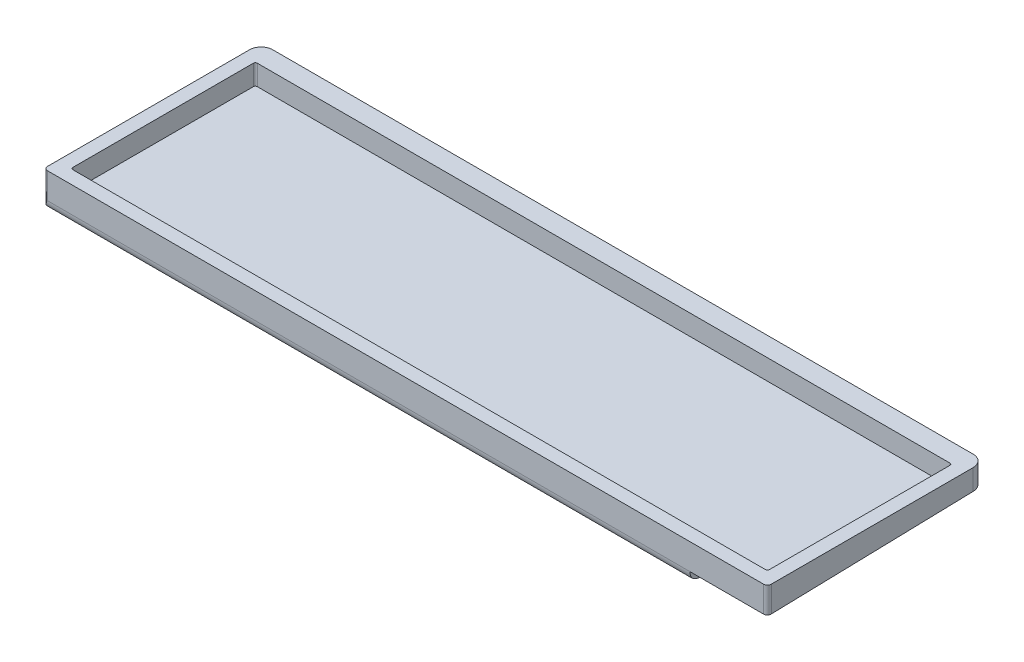
SolidWorks part; units mm, degrees
ref_plane "Front Plane" through (0, 0, 0) normal (0, 0, 1) x (1, 0, 0)
ref_plane "Top Plane" through (0, 0, 0) normal (0, 1, 0) x (1, 0, 0)
ref_plane "Right Plane" through (0, 0, 0) normal (1, 0, 0) x (0, 0, -1)
sketch "Sketch1" plane through (0, 0, 0) normal (0, 1, 0) x (1, 0, 0)
  line L1 (-178.825, 47.625) -> (178.825, 47.625)
  line L2 (-179.825, 46.625) -> (-179.825, -46.625)
  line L3 (-178.825, -47.625) -> (178.825, -47.625)
  line L4 (179.825, 46.625) -> (179.825, -46.625)
  line L5 (-179.825, 47.625) -> (179.825, -47.625) construction
  line L6 (-179.825, -47.625) -> (179.825, 47.625) construction
  arc A0 (178.825, -47.625) -> (179.825, -46.625) centre (178.825, -46.625) ccw
  arc A1 (178.825, 47.625) -> (179.825, 46.625) centre (178.825, 46.625) cw
  arc A2 (-179.825, -46.625) -> (-178.825, -47.625) centre (-178.825, -46.625) ccw
  arc A3 (-178.825, 47.625) -> (-179.825, 46.625) centre (-178.825, 46.625) ccw
  circle A4 centre (157.075, 19.175) radius 1.1
  circle A5 centre (136.925, -16.775) radius 1.1
  circle A6 centre (-153.475, 33.725) radius 1.1
  circle A7 centre (17.925, 22.275) radius 1.1
  circle A8 centre (17.875, -35.075) radius 1.1
  circle A9 centre (-130.375, -35.725) radius 1.1
  point P0 (0, 0)
  dimension "D3" = 1
  dimension "D4" = 2.2
  dimension "D7" = 2.2
  dimension "D8" = 2.2
  dimension "D9" = 2.2
  dimension "D10" = 2.2
  dimension "D11" = 2.2
  dimension "D1" = 359.65
  dimension "D2" = 95.25
  dimension "D5" = 22.75
  dimension "D6" = 28.45
  dimension "D12" = 42.9
  dimension "D13" = 30.85
  dimension "D14" = 25.35
  dimension "D15" = 161.9
  dimension "D16" = 12.55
  dimension "D17" = 161.95
  dimension "D18" = 11.9
  dimension "D19" = 49.45
  dimension "D20" = 13.9
  dimension "D21" = 26.35
sketch "Sketch2" plane through (0, 0, 0) normal (0, 1, 0) x (1, 0, 0)
  line L0 (-179.825, 46.625) -> (-179.825, -46.625) construction
  line L1 (-178.825, -47.625) -> (178.825, -47.625) construction
  line L2 (179.825, 46.625) -> (179.825, -46.625) construction
  line L3 (-178.825, 47.625) -> (178.825, 47.625) construction
  line L4 (-179.825, 46.625) -> (-179.825, -46.625)
  line L5 (-178.825, -47.625) -> (178.825, -47.625)
  line L6 (179.825, 46.625) -> (179.825, -46.625)
  line L7 (-178.825, 47.625) -> (178.825, 47.625)
  line L9 (-180.825, 57.625) -> (180.825, 57.625)
  line L10 (-186.825, 51.625) -> (-186.825, -52.625)
  line L11 (-184.825, -54.625) -> (184.825, -54.625)
  line L12 (186.825, 51.625) -> (186.825, -52.625)
  circle A0 centre (157.075, 19.175) radius 1.1 construction
  circle A1 centre (136.925, -16.775) radius 1.1 construction
  circle A2 centre (17.875, -35.075) radius 1.1 construction
  circle A3 centre (17.925, 22.275) radius 1.1 construction
  circle A4 centre (-153.475, 33.725) radius 1.1 construction
  circle A5 centre (-130.375, -35.725) radius 1.1 construction
  arc A6 (-179.825, -46.625) -> (-178.825, -47.625) centre (-178.825, -46.625) ccw construction
  arc A7 (178.825, -47.625) -> (179.825, -46.625) centre (178.825, -46.625) ccw construction
  arc A8 (179.825, 46.625) -> (178.825, 47.625) centre (178.825, 46.625) ccw construction
  arc A9 (-178.825, 47.625) -> (-179.825, 46.625) centre (-178.825, 46.625) ccw construction
  circle A10 centre (157.075, 19.175) radius 1.1
  circle A11 centre (136.925, -16.775) radius 1.1
  circle A12 centre (17.875, -35.075) radius 1.1
  circle A13 centre (17.925, 22.275) radius 1.1
  circle A14 centre (-153.475, 33.725) radius 1.1
  circle A15 centre (-130.375, -35.725) radius 1.1
  arc A16 (-179.825, -46.625) -> (-178.825, -47.625) centre (-178.825, -46.625) ccw
  arc A17 (178.825, -47.625) -> (179.825, -46.625) centre (178.825, -46.625) ccw
  arc A18 (179.825, 46.625) -> (178.825, 47.625) centre (178.825, 46.625) ccw
  arc A19 (-178.825, 47.625) -> (-179.825, 46.625) centre (-178.825, 46.625) ccw
  arc A20 (180.825, 57.625) -> (186.825, 51.625) centre (180.825, 51.625) cw
  arc A21 (-180.825, 57.625) -> (-186.825, 51.625) centre (-180.825, 51.625) ccw
  arc A22 (184.825, -54.625) -> (186.825, -52.625) centre (184.825, -52.625) ccw
  arc A23 (-186.825, -52.625) -> (-184.825, -54.625) centre (-184.825, -52.625) ccw
  point P30 (0, 0)
  dimension "D5" = 6
  dimension "D6" = 2
  dimension "D1" = 10
  dimension "D2" = 7
  dimension "D3" = 7
  dimension "D4" = 7
extrude "Boss-Extrude1" add sketch "Sketch2" along normal blind 10.5 contours L10 A23 L11 A22 L12 A20 L9 A21 A19 L7 A18 L6 A17 L5 A16 L4 region at (0, 0, -53.7235)
sketch "Sketch4" plane through (0, 0, 0) normal (0, -1, 0) x (1, 0, 0)
  line L0 (186.825, -51.625) -> (186.825, 52.625) construction
  line L1 (-180.825, -57.625) -> (180.825, -57.625) construction
  line L2 (-186.825, -51.625) -> (-186.825, 52.625) construction
  line L3 (-184.825, 54.625) -> (184.825, 54.625) construction
  line L4 (-179.825, 46.625) -> (-179.825, -46.625)
  line L5 (178.825, 47.625) -> (-178.825, 47.625)
  line L6 (179.825, -46.625) -> (179.825, 46.625)
  line L7 (-178.825, -47.625) -> (178.825, -47.625)
  line L8 (-179.825, 46.625) -> (-179.825, -46.625)
  line L10 (179.825, -46.625) -> (179.825, 46.625)
  line L11 (-178.825, -47.625) -> (178.825, -47.625)
  line L12 (186.825, -51.625) -> (186.825, 52.625)
  line L13 (-180.825, -57.625) -> (180.825, -57.625)
  line L14 (-186.825, -51.625) -> (-186.825, 52.625)
  line L15 (-184.825, 54.625) -> (184.825, 54.625)
  arc A0 (186.825, 52.625) -> (184.825, 54.625) centre (184.825, 52.625) ccw construction
  arc A1 (180.825, -57.625) -> (186.825, -51.625) centre (180.825, -51.625) ccw construction
  arc A2 (-186.825, -51.625) -> (-180.825, -57.625) centre (-180.825, -51.625) ccw construction
  arc A3 (-184.825, 54.625) -> (-186.825, 52.625) centre (-184.825, 52.625) ccw construction
  arc A4 (-179.825, -46.625) -> (-178.825, -47.625) centre (-178.825, -46.625) ccw
  arc A5 (-178.825, 47.625) -> (-179.825, 46.625) centre (-178.825, 46.625) ccw
  arc A6 (179.825, 46.625) -> (178.825, 47.625) centre (178.825, 46.625) ccw
  arc A7 (178.825, -47.625) -> (179.825, -46.625) centre (178.825, -46.625) ccw
  arc A8 (-179.825, -46.625) -> (-178.825, -47.625) centre (-178.825, -46.625) ccw
  arc A9 (-178.825, 47.625) -> (-179.825, 46.625) centre (-178.825, 46.625) ccw
  arc A10 (179.825, 46.625) -> (178.825, 47.625) centre (178.825, 46.625) ccw
  arc A11 (178.825, -47.625) -> (179.825, -46.625) centre (178.825, -46.625) ccw
  arc A12 (186.825, 52.625) -> (184.825, 54.625) centre (184.825, 52.625) ccw
  arc A13 (180.825, -57.625) -> (186.825, -51.625) centre (180.825, -51.625) ccw
  arc A14 (-186.825, -51.625) -> (-180.825, -57.625) centre (-180.825, -51.625) ccw
  arc A15 (-184.825, 54.625) -> (-186.825, 52.625) centre (-184.825, 52.625) ccw
  arc M9 (-178.825, -47.625) -> (-179.825, -46.625) centre (-178.825, -46.625) cw
  line M10 (-179.825, -46.625) -> (-179.825, 46.625)
  arc M11 (-179.825, 46.625) -> (-178.825, 47.625) centre (-178.825, 46.625) cw
  line M12 (-178.825, 47.625) -> (178.825, 47.625)
  arc M13 (178.825, 47.625) -> (179.825, 46.625) centre (178.825, 46.625) cw
  line M14 (179.825, 46.625) -> (179.825, -46.625)
  arc M15 (179.825, -46.625) -> (178.825, -47.625) centre (178.825, -46.625) cw
  line M16 (178.825, -47.625) -> (-178.825, -47.625)
  line M17 (-186.825, 52.625) -> (-186.825, -51.625)
  arc M18 (-186.825, -51.625) -> (-180.825, -57.625) centre (-180.825, -51.625) ccw
  line M19 (-180.825, -57.625) -> (180.825, -57.625)
  arc M20 (180.825, -57.625) -> (186.825, -51.625) centre (180.825, -51.625) ccw
  line M21 (186.825, -51.625) -> (186.825, 52.625)
  arc M22 (186.825, 52.625) -> (184.825, 54.625) centre (184.825, 52.625) ccw
  line M23 (184.825, 54.625) -> (-184.825, 54.625)
  arc M24 (-184.825, 54.625) -> (-186.825, 52.625) centre (-184.825, 52.625) ccw
  dimension "D1" = 0
extrude "Boss-Extrude3" add sketch "Sketch4" along normal blind 10.5 contours M24 M17 M18 M19 M20 M21 M22 M23 M16 M9 M10 M11 M12 M13 M14 M15 | M9 M16 M15 M14 M13 M12 M11 M10 region at (0, 0, 0) region at (182.3089, 0, -53.1089)
sketch "Sketch5" plane through (186.825, 0, 0) normal (1, 0, 0) x (0, 0, -1)
  line L0 (-54.625, 0) -> (57.625, 0) construction
  line L1 (-54.625, 10.5) -> (-54.625, -10.5) construction
  line L2 (57.625, 10.5) -> (57.625, -10.5) construction
  line L6 (51.625, -10.5) -> (-52.625, -10.5) construction
  line L7 (-38.125, -10.5) -> (57.625, 0)
  line L8 (-54.625, 0) -> (57.625, 0)
  line L9 (-54.625, -5.1933) -> (-52.625, -7.4293)
  line L10 (-54.625, -10.5) -> (-38.125, -10.5)
  line L11 (57.625, -10.5) -> (57.625, 0)
  line L12 (57.625, -10.5) -> (-38.125, -10.5)
  line L13 (-52.625, 10.5) -> (-52.625, -10.5) construction
  line L14 (-52.625, -7.4293) -> (-38.125, -10.5)
  line L15 (-54.625, 0) -> (-54.625, -5.1933)
  line L16 (-54.625, -5.1933) -> (-54.625, -10.5)
  line M5 (-52.625, 10.5) -> (-52.625, -10.5)
  line M6 (-52.625, -10.5) -> (51.625, -10.5)
  line M7 (51.625, -10.5) -> (51.625, 10.5)
  dimension "D1" = 3
  dimension "D2" = 14.5
extrude "Cut-Extrude1" cut sketch "Sketch5" against normal blind 400 contours L10 M5 | M5 M6 | L7 M6 M7 | L12 L11 L7 M7 region at (186.825, -7.2193, -21.7083) region at (186.825, -9.4764, 47.7917) region at (186.825, -5.4127, -54.6573) region at (186.825, -8.3559, 53.714)
fillet "Fillet2" radius 6 3 edges at (0, -10.5, 38.125) (0, -7.4293, 52.625) (0, -5.1933, 54.625) tangent propagation no
sketch "Sketch7" plane through (186.825, 0, 0) normal (1, 0, 0) x (0, 0, -1)
  line L0 (57.625, 0) -> (-54.625, -2.9015)
  line L5 (-54.625, -2.9015) -> (-54.625, -13.402)
  line L6 (-54.625, -13.402) -> (50.7578, -7.8685)
  line L7 (50.7578, -7.8685) -> (57.625, 0)
  point P2 (-54.625, 0.7879)
  point P8 (-54.625, -2.9015)
extrude "Cut-Extrude2" cut sketch "Sketch7" against normal blind 40
